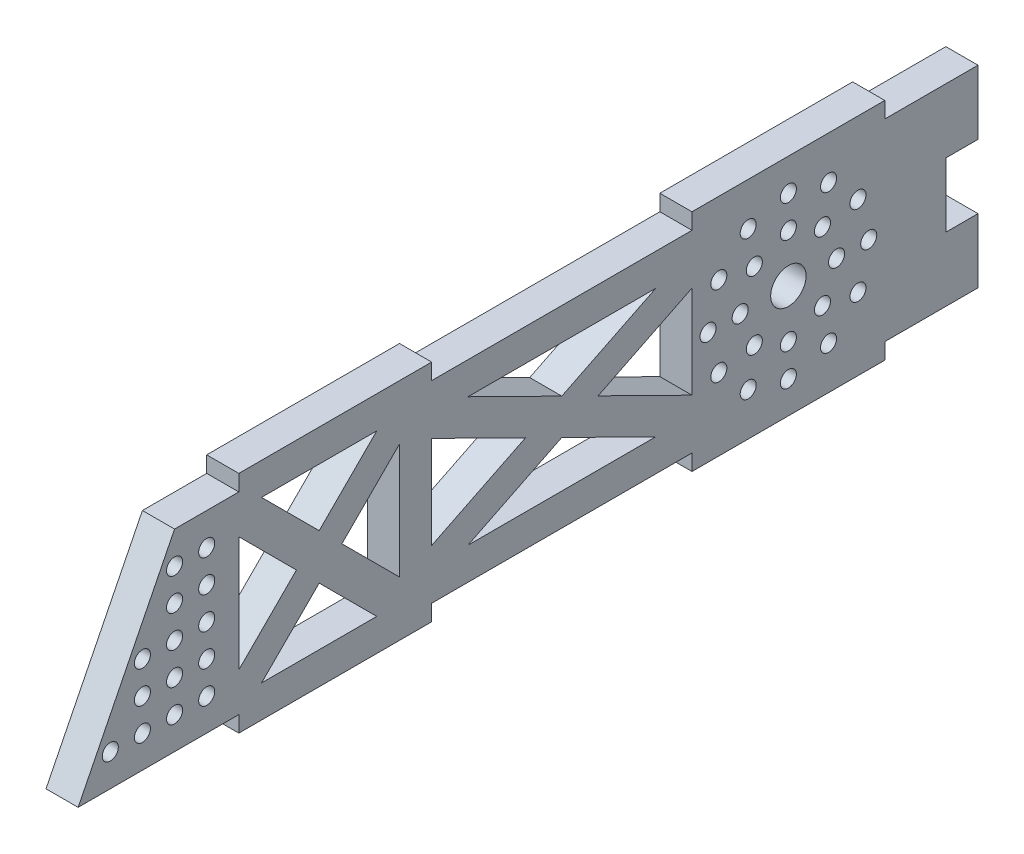
SolidWorks part; units mm, degrees
material "7050-T73510"
ref_plane "Front Plane" through (0, 0, 0) normal (0, 0, 1) x (1, 0, 0)
ref_plane "Top Plane" through (0, 0, 0) normal (0, 1, 0) x (1, 0, 0)
ref_plane "Right Plane" through (0, 0, 0) normal (1, 0, 0) x (0, 0, -1)
sketch "Sketch1" plane through (0, 0, 0) normal (1, 0, 0) x (0, 0, -1)
  line L1 (-177.8, -38.1) -> (177.8, -38.1)
  line L2 (-177.8, -38.1) -> (-177.8, 38.1)
  line L3 (-177.8, 38.1) -> (177.8, 38.1)
  line L4 (177.8, -38.1) -> (177.8, 38.1)
  line L5 (-177.8, -38.1) -> (177.8, 38.1) construction
  line L6 (-177.8, 38.1) -> (177.8, -38.1) construction
  point P0 (0, 0)
  dimension "D1" = 355.6
  dimension "D2" = 76.2
extrude "Boss-Extrude1" add sketch "Sketch1" along normal blind 12.7
sketch "Sketch2" plane through (12.7, 0, 0) normal (1, 0, 0) x (0, 0, -1)
  line L0 (-177.8, -38.1) -> (-139.7, 38.1)
  line L1 (177.8, 38.1) -> (-177.8, 38.1) construction
  dimension "D1" = 38.1
extrude "Cut-Extrude1" cut sketch "Sketch2" against normal through all and the other way through all
sketch "Sketch3" plane through (0, 0, 0) normal (-1, 0, 0) x (0, 0, 1)
  line L0 (177.8, -38.1) -> (-177.8, -38.1) construction
  line L1 (-140.97, -38.1) -> (-64.77, -38.1)
  line L2 (-140.97, -38.1) -> (-140.97, -44.45)
  line L3 (-140.97, -44.45) -> (-64.77, -44.45)
  line L4 (-64.77, -38.1) -> (-64.77, -44.45)
  line L5 (-177.8, -38.1) -> (-177.8, 38.1) construction
  line L6 (38.1, -38.1) -> (114.3, -38.1)
  line L7 (38.1, -38.1) -> (38.1, -44.45)
  line L8 (38.1, -44.45) -> (114.3, -44.45)
  line L9 (114.3, -38.1) -> (114.3, -44.45)
  line L10 (-177.8, 38.1) -> (139.7, 38.1) construction
  line L11 (-140.97, 38.1) -> (-64.77, 38.1)
  line L12 (-140.97, 38.1) -> (-140.97, 44.45)
  line L13 (-140.97, 44.45) -> (-64.77, 44.45)
  line L14 (-64.77, 38.1) -> (-64.77, 44.45)
  line L16 (38.1, 38.1) -> (114.3, 38.1)
  line L17 (38.1, 38.1) -> (38.1, 44.45)
  line L18 (38.1, 44.45) -> (114.3, 44.45)
  line L19 (114.3, 38.1) -> (114.3, 44.45)
  dimension "D1" = 76.2
  dimension "D2" = 6.35
  dimension "D3" = 76.2
  dimension "D4" = 6.35
  dimension "D5" = 36.83
  dimension "D6" = 215.9
  dimension "D7" = 76.2
  dimension "D8" = 6.35
  dimension "D9" = 6.35
  dimension "D10" = 76.2
extrude "Boss-Extrude2" add sketch "Sketch3" against normal blind 12.7
sketch "Sketch4" plane through (0, 0, 0) normal (-1, 0, 0) x (0, 0, 1)
  line L0 (-177.8, -38.1) -> (-177.8, 38.1) construction
  line L1 (-177.8, 12.7) -> (-165.1, 12.7)
  line L2 (-177.8, 12.7) -> (-177.8, -12.7)
  line L3 (-177.8, -12.7) -> (-165.1, -12.7)
  line L4 (-165.1, 12.7) -> (-165.1, -12.7)
  line L5 (-140.97, -38.1) -> (-177.8, -38.1) construction
  line L6 (-177.8, 38.1) -> (-140.97, 38.1) construction
  dimension "D1" = 25.4
  dimension "D2" = 25.4
  dimension "D3" = 12.7
extrude "Cut-Extrude2" cut sketch "Sketch4" against normal through all
sketch "Sketch5" plane through (0, 0, 0) normal (-1, 0, 0) x (0, 0, 1)
  line L0 (-165.1, -12.7) -> (-165.1, 12.7) construction
  line L1 (-140.97, -38.1) -> (-177.8, -38.1) construction
  circle A0 centre (-102.87, 0) radius 7
  dimension "D1" = 62.23
  dimension "D3" = 14
  dimension "D2" = 38.1
extrude "Cut-Extrude3" cut sketch "Sketch5" against normal through all
sketch "Sketch6" plane through (0, 0, 0) normal (-1, 0, 0) x (0, 0, 1)
  line L0 (38.1, -38.1) -> (-64.77, -38.1) construction
  line L1 (-64.77, 25.4) -> (38.1, 25.4)
  line L2 (-64.77, 25.4) -> (-64.77, -25.4)
  line L3 (-64.77, -25.4) -> (38.1, -25.4)
  line L4 (38.1, 25.4) -> (38.1, -25.4)
  line L5 (-64.77, 38.1) -> (38.1, 38.1) construction
  line L6 (38.1, 44.45) -> (38.1, 38.1) construction
  line L7 (-64.77, 38.1) -> (-64.77, 44.45) construction
  line L8 (-64.77, 25.4) -> (38.1, -25.4) construction
  line L9 (-64.77, -25.4) -> (38.1, 25.4) construction
  line L10 (-50.4288, -25.4) -> (-13.335, -7.0821)
  line L11 (23.7588, 25.4) -> (-13.335, 7.0821)
  line L12 (-50.4288, 25.4) -> (-13.335, 7.0821)
  line L13 (23.7588, -25.4) -> (-13.335, -7.0821)
  line L14 (1.0062, 0) -> (38.1, 18.3179)
  line L15 (-27.6762, 0) -> (-64.77, 18.3179)
  line L16 (1.0062, 0) -> (38.1, -18.3179)
  line L17 (-27.6762, 0) -> (-64.77, -18.3179)
  line L18 (38.1, -44.45) -> (114.3, -44.45) construction
  line L19 (50.8, 31.75) -> (114.3, 31.75)
  line L20 (50.8, 31.75) -> (50.8, -31.75)
  line L21 (50.8, -31.75) -> (114.3, -31.75)
  line L22 (114.3, 31.75) -> (114.3, -31.75)
  line L23 (114.3, 44.45) -> (38.1, 44.45) construction
  line L26 (114.3, 38.1) -> (114.3, 44.45) construction
  line L28 (50.8, -31.75) -> (114.3, 31.75) construction
  line L29 (114.3, -31.75) -> (50.8, 31.75) construction
  line L30 (59.7803, -31.75) -> (114.3, 22.7697)
  line L31 (50.8, -22.7697) -> (105.3197, 31.75)
  line L32 (114.3, -22.7697) -> (59.7803, 31.75)
  line L33 (105.3197, -31.75) -> (50.8, 22.7697)
  point P36 (114.3, 41.275)
  dimension "D1" = 12.7
  dimension "D2" = 12.7
  dimension "D3" = 12.7
  dimension "D4" = 12.7
  dimension "D5" = 12.7
  dimension "D6" = 12.7
  dimension "D7" = 12.7
  dimension "D8" = 0
  dimension "D9" = 12.7
  dimension "D10" = 12.7
extrude "Cut-Extrude4" cut sketch "Sketch6" against normal through all contours L3 L13 L10 | L17 L15 L2 | L1 L12 L11 | L14 L16 L4 | L21 L33 L30 | L32 L22 L30 | L31 L33 L20 | L32 L31 L19 region at (0, 19.294, -13.335) region at (0, 0, -52.4054) region at (0, 0, 25.7354) region at (0, -19.294, -13.335) region at (0, 24.1601, 82.55) region at (0, 0, 58.3899) region at (0, 0, 106.7101) region at (0, -24.1601, 82.55)
sketch "Sketch7" plane through (12.7, 0, 0) normal (1, 0, 0) x (0, 0, -1)
  line L0 (-114.3, 38.1) -> (-139.7, 38.1) construction
  line L2 (-114.3, 22.7697) -> (-114.3, -22.7697) construction
  circle A0 centre (121.92, 0) radius 3.175
  circle A1 centre (102.87, 0) radius 7 construction
  circle A2 centre (134.62, 0) radius 3.175
  circle A3 centre (116.3404, -13.4704) radius 3.175
  circle A4 centre (102.87, -19.05) radius 3.175
  circle A5 centre (89.3996, -13.4704) radius 3.175
  circle A6 centre (83.82, 0) radius 3.175
  circle A7 centre (89.3996, 13.4704) radius 3.175
  circle A8 centre (102.87, 19.05) radius 3.175
  circle A9 centre (116.3404, 13.4704) radius 3.175
  circle A10 centre (130.3663, -15.875) radius 3.175
  circle A11 centre (118.745, -27.4963) radius 3.175
  circle A12 centre (102.87, -31.75) radius 3.175
  circle A13 centre (86.995, -27.4963) radius 3.175
  circle A14 centre (75.3737, -15.875) radius 3.175
  circle A15 centre (71.12, 0) radius 3.175
  circle A16 centre (75.3737, 15.875) radius 3.175
  circle A17 centre (86.995, 27.4963) radius 3.175
  circle A18 centre (102.87, 31.75) radius 3.175
  circle A19 centre (118.745, 27.4963) radius 3.175
  circle A20 centre (130.3663, 15.875) radius 3.175
  circle A21 centre (-127, 25.4) radius 3.175
  circle A22 centre (-127, 12.7) radius 3.175
  circle A23 centre (-127, 0) radius 3.175
  circle A24 centre (-127, -12.7) radius 3.175
  circle A25 centre (-127, -25.4) radius 3.175
  circle A26 centre (-139.7, 12.7) radius 3.175
  circle A27 centre (-139.7, 0) radius 3.175
  circle A28 centre (-139.7, -12.7) radius 3.175
  circle A29 centre (-139.7, -25.4) radius 3.175
  circle A31 centre (-152.4, 0) radius 3.175
  circle A32 centre (-152.4, -12.7) radius 3.175
  circle A33 centre (-152.4, -25.4) radius 3.175
  circle A37 centre (-165.1, -25.4) radius 3.175
  circle A38 centre (-139.7, 25.4) radius 3.175
  circle A41 centre (-165.1, 25.4) radius 3.175 [skipped]
  circle A42 centre (-152.4, 25.4) radius 3.175 [skipped]
  circle A43 centre (-152.4, 12.7) radius 3.175 [skipped]
  circle A44 centre (-165.1, 0) radius 3.175 [skipped]
  circle A45 centre (-165.1, -12.7) radius 3.175 [skipped]
  circle A46 centre (-165.1, 12.7) radius 3.175 [skipped]
  point P22 (102.87, 0)
  point P46 (102.87, 0)
  dimension "D1" = 6.35
  dimension "D3" = 6.35
  dimension "D7" = 12.7
  dimension "D2" = 19.05
  dimension "D4" = 12.7
  dimension "D8" = 12.7
  dimension "D9" = 5
  dimension "D10" = 4
  dimension "D5" = 8
  dimension "D6" = 12
extrude "Cut-Extrude5" cut sketch "Sketch7" against normal through all
